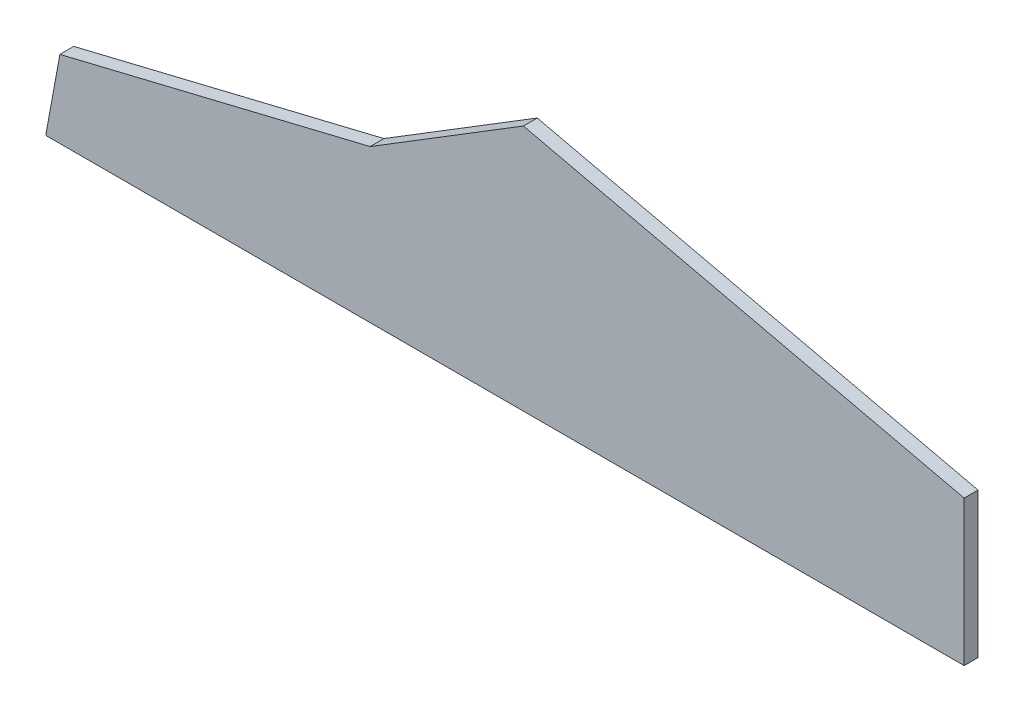
SolidWorks part; units mm, degrees
ref_plane "Front Plane" through (0, 0, 0) normal (0, 0, 1) x (1, 0, 0)
ref_plane "Top Plane" through (0, 0, 0) normal (0, 1, 0) x (1, 0, 0)
ref_plane "Right Plane" through (0, 0, 0) normal (1, 0, 0) x (0, 0, -1)
sketch "Sketch2" plane through (0, 0, 0) normal (0, 0, 1) x (1, 0, 0)
  line L0 (-318.7974, 52.106) -> (-105.4374, 103.886)
  line L1 (-105.4374, 103.886) -> (0, 168.8465)
  line L2 (0, 168.8465) -> (303.0919, 98.8)
  line L3 (303.0919, 98.8) -> (303.0919, 0)
  line L4 (303.0919, 0) -> (303.0919, -1)
  line L6 (303.0919, -1) -> (-328.3315, -1)
  line L7 (-328.3315, -1) -> (-328.3315, 0)
  spline S0 degree 1 poles (-328.3315, 0) (-318.7974, 52.106) knots 0 0 1 1
  dimension "D1" = 9.5341
  dimension "D2" = 52.106
  dimension "D3" = 213.36
  dimension "D4" = 51.78
  dimension "D5" = 105.4374
  dimension "D6" = 64.9605
  dimension "D7" = 303.0919
  dimension "D8" = 98.8
  dimension "D9" = 1
extrude "Boss-Extrude1" add sketch "Sketch2" along normal mid plane 9.525
